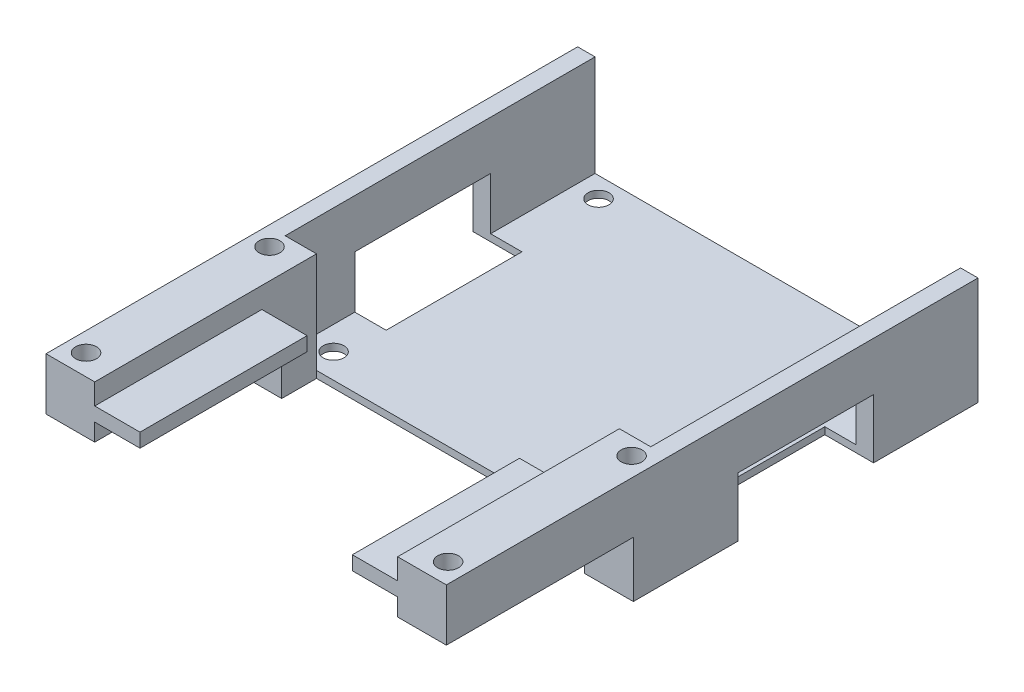
SolidWorks part; units mm, degrees
ref_plane "Front Plane" through (0, 0, 0) normal (0, 0, 1) x (1, 0, 0)
ref_plane "Top Plane" through (0, 0, 0) normal (0, 1, 0) x (1, 0, 0)
ref_plane "Right Plane" through (0, 0, 0) normal (1, 0, 0) x (0, 0, -1)
sketch "Sketch1" plane through (0, 0, 0) normal (0, 1, 0) x (1, 0, 0)
  line L0 (0, 0) -> (0, 76.35) construction
  line L1 (-28.75, 76.35) -> (28.75, 76.35)
  line L2 (28.75, 76.35) -> (28.75, 0)
  line L3 (28.75, 0) -> (21.75, 0)
  line L4 (21.75, 0) -> (21.75, 31.85)
  line L5 (21.75, 31.85) -> (-21.75, 31.85)
  line L6 (-21.75, 31.85) -> (-21.75, 0)
  line L7 (-21.75, 0) -> (-28.75, 0)
  line L8 (-28.75, 0) -> (-28.75, 76.35)
  line L9 (-26.25, 76.35) -> (-26.25, 31.85)
  line L14 (-26.25, 31.85) -> (-21.75, 31.85)
  line L15 (26.25, 76.35) -> (26.25, 31.85)
  line L16 (26.25, 31.85) -> (21.75, 31.85)
  line L17 (28.75, 74.35) -> (30.25, 74.35)
  line L18 (-28.75, 41.35) -> (-26.25, 41.35)
  line L19 (-28.75, 41.35) -> (-28.75, 53.35)
  line L20 (-28.75, 53.35) -> (-26.25, 53.35)
  line L21 (-26.25, 41.35) -> (-26.25, 53.35)
  line L22 (30.25, 68.35) -> (28.75, 68.35)
  line L23 (-30.25, 68.35) -> (-28.75, 68.35)
  line L24 (-28.75, 74.35) -> (-30.25, 74.35)
  arc A0 (30.25, 68.35) -> (30.25, 74.35) centre (30.25, 71.35) ccw
  arc A1 (-30.25, 68.35) -> (-30.25, 74.35) centre (-30.25, 71.35) cw
  point P10 (0, 76.35)
  point P16 (-27.5, 41.35)
  point P17 (-22.85, 73.45)
  point P18 (22.85, 73.45)
  point P23 (22.85, 35.4)
  point P24 (-22.85, 35.4)
  point P25 (26, 3)
  point P26 (26, 29.35)
  point P27 (-26, 29.35)
  point P28 (-26, 3)
  point P40 (30.25, 71.35)
  point P41 (-30.25, 71.35)
  dimension "D16" = 3
  dimension "D1" = 2.5
  dimension "D2" = 7
  dimension "D3" = 43.5
  dimension "D4" = 31.85
  dimension "D5" = 44.5
  dimension "D6" = 23
  dimension "D7" = 12
  dimension "D8" = 22.85
  dimension "D9" = 38.05
  dimension "D10" = 2.9
  dimension "D11" = 52
  dimension "D12" = 52
  dimension "D13" = 47
  dimension "D14" = 3
  dimension "D15" = 1.5
  dimension "D17" = 2
extrude "Boss-Extrude1" add sketch "Sketch1" along normal blind 1 contours L5 L0 L1 L9 L14 | L0 L5 L16 L15 L1 region at (-13.125, 0, -54.1) region at (13.125, 0, -54.1)
extrude "Boss-Extrude2" add sketch "Sketch1<3>" along normal blind 15.5 contours L18 L8 L7 L6 L14 L9 | L8 L20 L9 L1 | L15 L16 L4 L3 L2 L1 | L20 L8 L18 L9 region at (-27.5, 0, -64.85) region at (25.999, 0, -28.6329) region at (-27.5, 0, -47.35) region at (-25.4666, 0, -17.9154)
sketch "Sketch1<3>" plane through (0, 0, 0) normal (0, 1, 0) x (1, 0, 0) same geometry as "Sketch1"
hole_wizard "Ø3.0 (3) Diameter Hole1" positions "Sketch4" profile "Sketch5" hole size "Ø3.0" standard "ANSI Metric" end condition through all
sketch "Sketch4" plane through (0, 0, 0) normal (0, -1, 0) x (-1, 0, 0)
  point P0 (-22.85, 73.45)
  point P3 (22.85, 73.45)
  point P6 (26, 29.35)
  point P9 (22.85, 35.4)
  point P12 (-22.85, 35.4)
  point P15 (-26, 29.35)
  point P18 (-26, 3)
  point P21 (26, 3)
  point P24 (-30.25, 71.35)
  point P27 (30.25, 71.35)
sketch "Sketch5" plane through (22.85, 0, -73.45) normal (1, 0, 0) x (0, 0, -1)
  line L0 (0, 0) -> (0, 15.5)
  line L1 (0, 15.5) -> (1.5, 15.5)
  line L2 (1.5, 15.5) -> (1.5, 0)
  line L5 (1.5, 0) -> (0, 0)
  line L11 (0, -6.35) -> (0, 107.95) construction
  dimension "Thru Hole Dia." = 3
  dimension "Thru Hole Depth" = 15.5
sketch "Sketch6" plane through (0, 0, 0) normal (0, 0, 1) x (1, 0, 0)
  line L0 (-21.75, 15.5) -> (-21.75, 0) construction
  line L5 (0, -1.6497) -> (0, 21.9352) construction
  line L6 (-21.75, 10.5) -> (-15.25, 10.5)
  line L7 (-21.75, 10.5) -> (-21.75, 12.5)
  line L8 (-21.75, 12.5) -> (-15.25, 12.5)
  line L9 (-15.25, 10.5) -> (-15.25, 12.5)
  line L10 (-28.75, 15.5) -> (-28.75, 0) construction
  line L11 (-20.25, 10.5) -> (-21.75, 10.5)
  line L12 (-20.25, 10.5) -> (-20.25, 8)
  line L13 (-20.25, 8) -> (-21.75, 8)
  line L14 (-21.75, 10.5) -> (-21.75, 8)
  line L15 (-21.75, 0) -> (-28.75, 0)
  line L16 (-21.75, 0) -> (-21.75, 8)
  line L17 (-21.75, 8) -> (-28.75, 8)
  line L18 (-28.75, 0) -> (-28.75, 8)
  line L19 (28.75, 0) -> (28.75, 8)
  line L20 (21.75, 8) -> (28.75, 8)
  line L21 (21.75, 0) -> (21.75, 8)
  line L22 (21.75, 0) -> (28.75, 0)
  line L23 (21.75, 10.5) -> (21.75, 8)
  line L24 (20.25, 8) -> (21.75, 8)
  line L25 (20.25, 10.5) -> (20.25, 8)
  line L26 (20.25, 10.5) -> (21.75, 10.5)
  line L27 (15.25, 10.5) -> (15.25, 12.5)
  line L28 (21.75, 12.5) -> (15.25, 12.5)
  line L29 (21.75, 10.5) -> (21.75, 12.5)
  line L30 (21.75, 10.5) -> (15.25, 10.5)
  line L31 (-21.75, 15.5) -> (-28.75, 15.5) construction
  line M21 (21.75, 0) -> (28.75, 0)
  line M22 (28.75, 0) -> (28.75, 15.5)
  line M24 (21.75, 15.5) -> (21.75, 0)
  dimension "D1" = 6.5
  dimension "D2" = 3
  dimension "D3" = 2
  dimension "D4" = 2.5
  dimension "D5" = 1.5
extrude "Boss-Extrude3" add sketch "Sketch6" against normal blind 24 contours L30 L26 L28 L27 M24 | L6 L9 L8 L7 region at (-18.5, 11.5, 0) region at (18.5, 11.5, 0)
extrude "Cut-Extrude1" cut sketch "Sketch6<4>" against normal blind 26.85 contours L18 L15 L16 L17 | L20 M24 M21 M22 region at (-25.25, 4, 0) region at (25.25, 4, 0)
sketch "Sketch6<4>" plane through (0, 0, 0) normal (0, 0, 1) x (1, 0, 0) same geometry as "Sketch6"
sketch "Sketch8" plane through (0, 0, 0) normal (0, -1, 0) x (1, 0, 0)
  line L0 (0, 17.5937) -> (0, -89.2896) construction
  line L1 (-28.75, -61.35) -> (-21.75, -61.35)
  line L2 (-28.75, -61.35) -> (-28.75, -41.85)
  line L3 (-28.75, -41.85) -> (-21.75, -41.85)
  line L4 (-21.75, -61.35) -> (-21.75, -41.85)
  line L6 (-28.75, -76.35) -> (28.75, -76.35) construction
  line L8 (21.75, -61.35) -> (21.75, -41.85)
  line L9 (28.75, -41.85) -> (21.75, -41.85)
  line L10 (28.75, -61.35) -> (28.75, -41.85)
  line L11 (28.75, -61.35) -> (21.75, -61.35)
  line L12 (-28.75, -26.85) -> (-28.75, -76.35) construction
  dimension "D1" = 15
  dimension "D2" = 7
  dimension "D3" = 19.5
extrude "Cut-Extrude2" cut sketch "Sketch8" against normal blind 8.5
sketch "Sketch9" plane through (0, 0, 0) normal (0, -1, 0) x (1, 0, 0)
  line L0 (-3.6898, -66.9636) -> (-0.7669, -56.1918)
  line L1 (-0.7669, -56.1918) -> (-9.5993, -56.1918)
  line L2 (-9.5993, -56.1918) -> (4.2079, -40.0618)
  line L3 (4.2079, -40.0618) -> (3.001, -51.0446)
  line L4 (3.001, -51.0446) -> (10.9951, -51.0446)
  line L5 (10.9951, -51.0446) -> (-3.6898, -66.9636)
extrude "Cut-Extrude3" cut sketch "Sketch9" against normal blind 0.3
equation "\"D1@Boss-Extrude2\"=16.000000mm-0.5"
